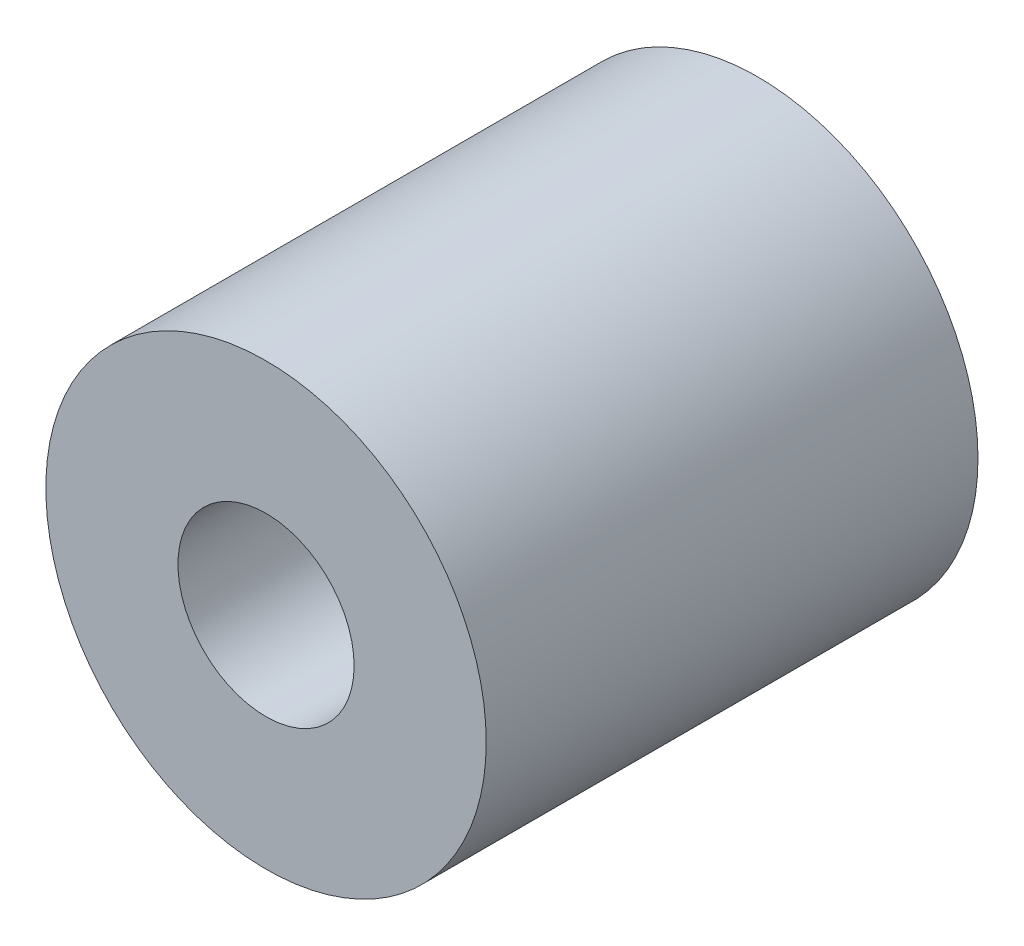
SolidWorks part; units mm, degrees
material "Alloy Steel"
ref_plane "Front Plane" through (0, 0, 0) normal (0, 0, 1) x (1, 0, 0)
ref_plane "Top Plane" through (0, 0, 0) normal (0, 1, 0) x (1, 0, 0)
ref_plane "Right Plane" through (0, 0, 0) normal (1, 0, 0) x (0, 0, -1)
sketch "Sketch1" plane through (0, 0, 0) normal (0, 0, 1) x (1, 0, 0)
  circle A0 centre (0, 0) radius 6
  circle A1 centre (0, 0) radius 15
  dimension "D1" = 12
  dimension "D2" = 30
extrude "Boss-Extrude1" add sketch "Sketch1" along normal blind 33.5
